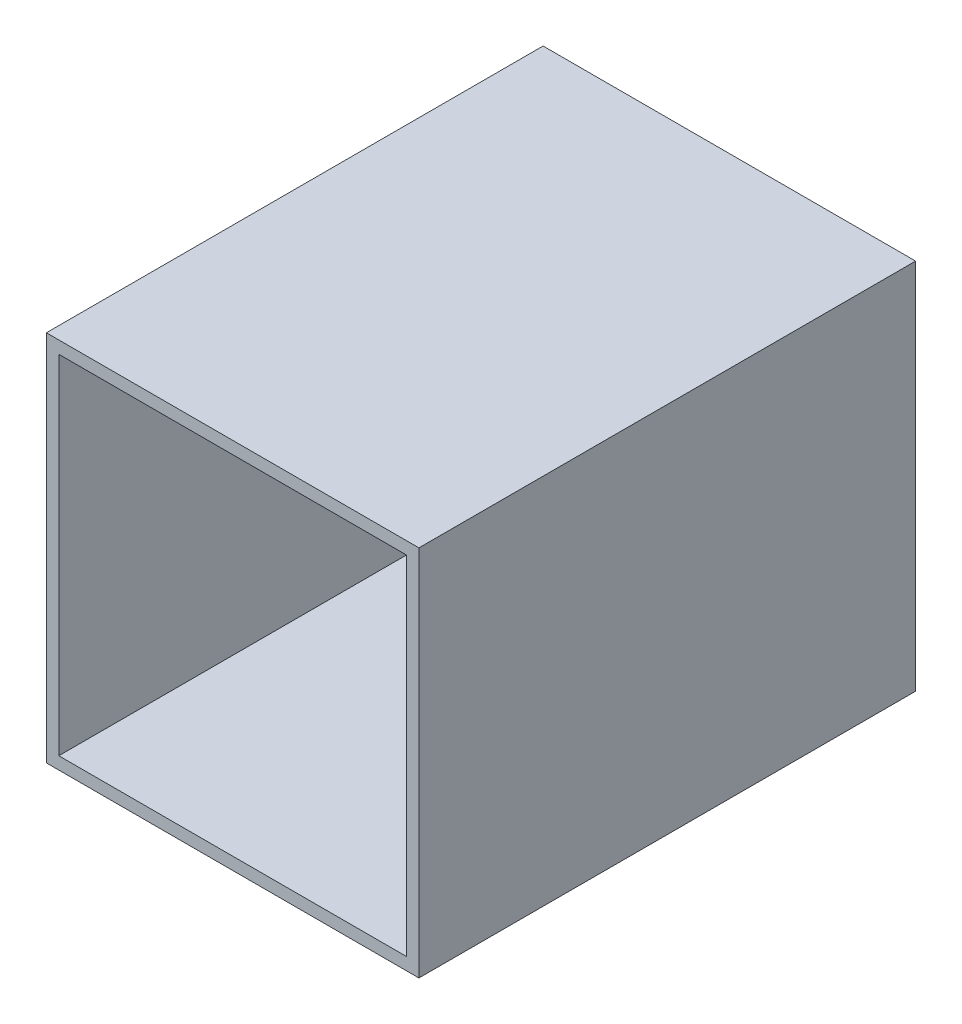
SolidWorks part; units mm, degrees
ref_plane "Front Plane" through (0, 0, 0) normal (0, 0, 1) x (1, 0, 0)
ref_plane "Top Plane" through (0, 0, 0) normal (0, 1, 0) x (1, 0, 0)
ref_plane "Right Plane" through (0, 0, 0) normal (1, 0, 0) x (0, 0, -1)
sketch "Sketch1" plane through (0, 0, 0) normal (0, 1, 0) x (1, 0, 0)
  line L1 (-38.1, -50.8) -> (38.1, -50.8)
  line L2 (-38.1, -50.8) -> (-38.1, 50.8)
  line L3 (-38.1, 50.8) -> (38.1, 50.8)
  line L4 (38.1, -50.8) -> (38.1, 50.8)
  line L5 (-38.1, -50.8) -> (38.1, 50.8) construction
  line L6 (-38.1, 50.8) -> (38.1, -50.8) construction
  point P0 (0, 0)
  dimension "D1" = 101.6
  dimension "D2" = 76.2
extrude "box" add sketch "Sketch1" along normal blind 76.2
shell "hollow it" thickness 2.54 removed face at (0, 38.1, 50.8)
sketch "Sketch2" plane through (0, 0, -50.8) normal (0, 0, -1) x (-1, 0, 0)
  line L0 (-38.1, 76.2) -> (38.1, 76.2) construction
  line L1 (-27.94, 69.85) -> (-20.32, 69.85)
  line L2 (-27.94, 69.85) -> (-27.94, 6.35)
  line L3 (-27.94, 6.35) -> (-20.32, 6.35)
  line L4 (-20.32, 69.85) -> (-20.32, 6.35)
  line L6 (-38.1, 76.2) -> (-38.1, 0) construction
  dimension "D1" = 7.62
  dimension "D2" = 63.5
  dimension "D3" = 6.35
  dimension "D4" = 10.16
extrude "slider track" cut sketch "Sketch2" against normal up to surface (2.54 mm away) up to face at (0, 38.1, -48.26)
sketch "Sketch4" plane through (0, 0, -50.8) normal (0, 0, -1) x (-1, 0, 0)
  line L0 (-38.1, 76.2) -> (38.1, 76.2) construction
  circle A0 centre (0, 57.15) radius 6.35
  dimension "D1" = 12.7
  dimension "D2" = 19.05
extrude "button large ring" cut sketch "Sketch4" against normal blind 1.27
sketch "Sketch5" plane through (0, 0, -49.53) normal (0, 0, -1) x (-1, 0, 0)
  circle A0 centre (0, 57.15) radius 3.175
  circle A1 centre (0, 57.15) radius 6.35 construction
  dimension "D2" = 6.35
  dimension "D1" = 0
extrude "button small hole" cut sketch "Sketch5" against normal blind 1.27
sketch "Sketch6" plane through (0, 0, -50.8) normal (0, 0, -1) x (-1, 0, 0)
  line L0 (-3.2977, 25.4) -> (-3.2977, 31.75)
  line L1 (-3.2977, 31.75) -> (3.0523, 31.75)
  line L2 (3.0523, 31.75) -> (3.0523, 25.4)
  line L3 (3.0523, 25.4) -> (9.4023, 25.4)
  line L4 (9.4023, 25.4) -> (9.4023, 19.05)
  line L5 (9.4023, 19.05) -> (3.0523, 19.05)
  line L6 (3.0523, 19.05) -> (3.0523, 12.7)
  line L7 (3.0523, 12.7) -> (-3.2977, 12.7)
  line L8 (-3.2977, 12.7) -> (-3.2977, 19.05)
  line L9 (-3.2977, 19.05) -> (-9.6477, 19.05)
  line L10 (-9.6477, 19.05) -> (-9.6477, 25.4)
  line L11 (-9.6477, 25.4) -> (-3.2977, 25.4)
  line L12 (-38.1, 0) -> (38.1, 0) construction
  dimension "D1" = 6.35
  dimension "D2" = 6.35
  dimension "D3" = 6.35
  dimension "D4" = 6.35
  dimension "D5" = 6.35
  dimension "D6" = 6.35
  dimension "D7" = 6.35
  dimension "D8" = 6.35
  dimension "D9" = 6.35
  dimension "D10" = 12.7
extrude "dpad large shape" cut sketch "Sketch6" against normal blind 1.27
sketch "Sketch7" plane through (0, 0, -49.53) normal (0, 0, -1) x (-1, 0, 0)
  line L0 (-3.2977, 25.4) -> (-9.6477, 25.4) construction
  line L1 (-9.6477, 25.4) -> (-9.6477, 19.05) construction
  line L2 (3.0523, 12.7) -> (3.0523, 19.05) construction
  line L3 (-3.2977, 12.7) -> (3.0523, 12.7) construction
  line L4 (3.0523, 19.05) -> (9.4023, 19.05) construction
  line L5 (9.4023, 19.05) -> (9.4023, 25.4) construction
  line L6 (3.0523, 25.4) -> (3.0523, 31.75) construction
  line L7 (-3.2977, 31.75) -> (-3.2977, 25.4) construction
  line L8 (3.0523, 31.75) -> (-3.2977, 31.75) construction
  circle A0 centre (-0.1227, 28.575) radius 1.397
  circle A1 centre (6.2273, 22.225) radius 1.397
  circle A2 centre (-0.1227, 15.875) radius 1.397
  circle A3 centre (-6.4727, 22.225) radius 1.397
  point P12 (3.0523, 15.875)
  point P17 (6.2273, 19.05)
  dimension "D3" = 2.794
  dimension "D6" = 2.794
  dimension "D9" = 2.794
  dimension "D13" = 2.794
  dimension "D1" = 3.175
  dimension "D2" = 3.175
  dimension "D4" = 3.175
  dimension "D5" = 3.175
  dimension "D7" = 3.175
  dimension "D8" = 3.175
  dimension "D10" = 3.175
  dimension "D11" = 3.175
  dimension "D12" = 3.175
extrude "dpad tiny holes" cut sketch "Sketch7" against normal blind 1.27
sketch "Sketch8" plane through (0, 0, -50.8) normal (0, 0, -1) x (-1, 0, 0)
  line L0 (38.1, 76.2) -> (38.1, 0) construction
  circle A0 centre (21.336, 43.0507) radius 12.7
  dimension "D1" = 25.4
  dimension "D2" = 16.764
extrude "dial large ring" cut sketch "Sketch8" against normal blind 1.27
ref_point "dial center"
sketch "Sketch9" plane through (0, 0, -49.53) normal (0, 0, -1) x (-1, 0, 0)
  circle A0 centre (21.336, 43.0507) radius 3.175
  dimension "D1" = 6.35
extrude "dial small hole" cut sketch "Sketch9" against normal blind 1.27
